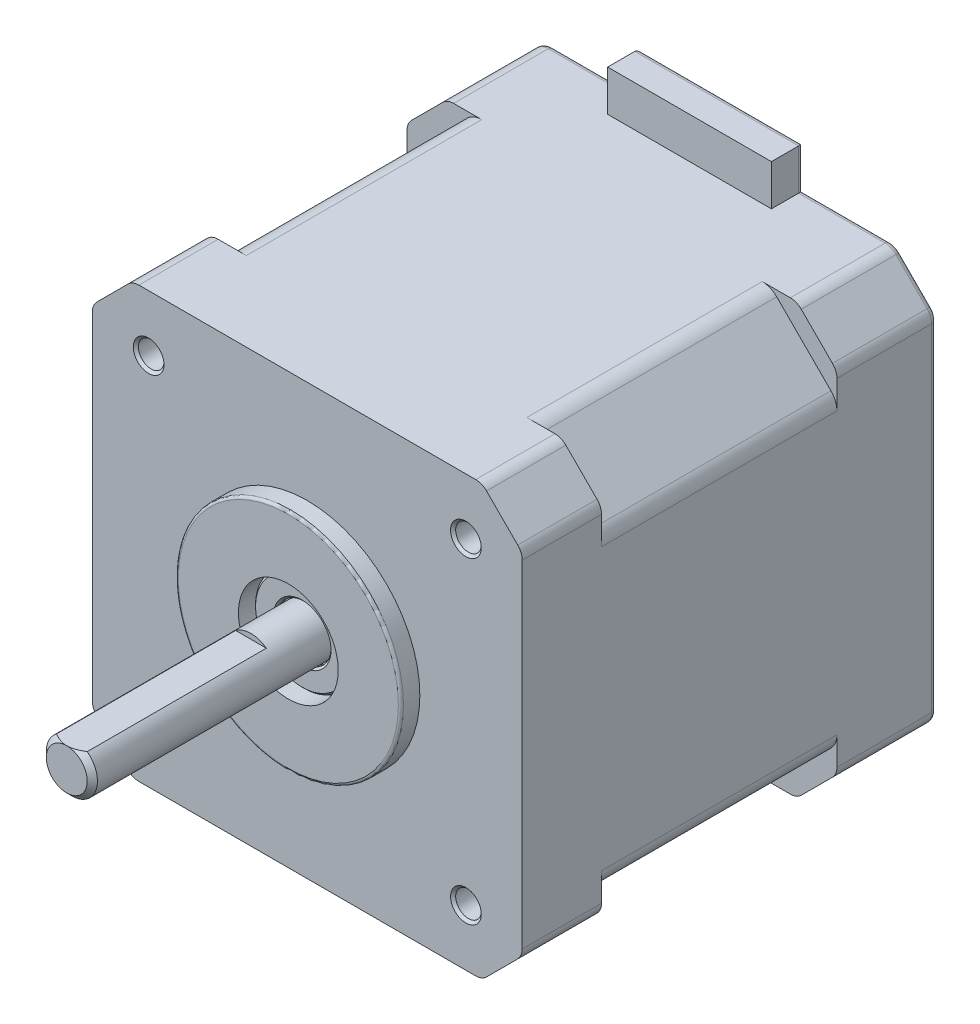
SolidWorks part; units mm, degrees
ref_plane "前视基准面" through (0, 0, 0) normal (0, 0, 1) x (1, 0, 0)
ref_plane "上视基准面" through (0, 0, 0) normal (0, 1, 0) x (1, 0, 0)
ref_plane "右视基准面" through (0, 0, 0) normal (1, 0, 0) x (0, 0, -1)
other "Configuration Table"
sketch "草图1" plane through (0, 0, 0) normal (0, 0, 1) x (1, 0, 0)
  line L1 (-21, 21) -> (21, 21)
  line L2 (-21, 21) -> (-21, -21)
  line L3 (-21, -21) -> (21, -21)
  line L4 (21, 21) -> (21, -21)
  line L5 (-21, 21) -> (21, -21) construction
  line L6 (-21, -21) -> (21, 21) construction
  point P0 (0, 0)
  dimension "D1" = 42
extrude "凸台-拉伸1" add sketch "草图1" along normal blind 40.5
sketch "草图2" plane through (0, 0, 0) normal (0, 0, -1) x (-1, 0, 0)
  line L0 (-21, 21) -> (21, 21) construction
  line L1 (8, 21) -> (-8, 21)
  line L2 (8, 21) -> (8, 25)
  line L3 (8, 25) -> (-8, 25)
  line L4 (-8, 21) -> (-8, 25)
  line L5 (0, 0) -> (0, 31.1942) construction
  dimension "D1" = 16
  dimension "D2" = 4
extrude "凸台-拉伸2" add sketch "草图2" against normal blind 3.15
sketch "草图3" plane through (0, 0, 0) normal (0, 0, -1) x (-1, 0, 0)
  line L0 (-17.075, 21) -> (-21, 17.075)
  line L1 (-21, 21) -> (-8, 21) construction
  line L2 (-21, -21) -> (-21, 21) construction
  line L3 (17.075, 21) -> (21, 17.075)
  line L4 (8, 21) -> (21, 21) construction
  line L5 (21, 21) -> (21, -21) construction
  line L6 (21, -17.075) -> (17.075, -21)
  line L7 (21, -21) -> (-21, -21) construction
  line L8 (-21, -17.075) -> (-17.075, -21)
  line L9 (-17.075, 21) -> (-21, 21)
  line L10 (-21, 21) -> (-21, 17.075)
  line L11 (17.075, 21) -> (21, 21)
  line L12 (21, 21) -> (21, 17.075)
  line L13 (21, -17.075) -> (21, -21)
  line L14 (21, -21) -> (17.075, -21)
  line L15 (-21, -17.075) -> (-21, -21)
  line L16 (-21, -21) -> (-17.075, -21)
  dimension "D1" = 3.925
extrude "切除-拉伸1" cut sketch "草图3" against normal up to next
sketch "草图4" plane through (0, 0, 0) normal (0, 0, -1) x (-1, 0, 0)
  line L0 (-21, 14.532) -> (-14.532, 21)
  line L1 (-21, -17.075) -> (-21, 17.075) construction
  line L2 (-17.075, 21) -> (-8, 21) construction
  line L3 (-14.532, 21) -> (-21, 21)
  line L4 (-21, 21) -> (-21, 14.532)
  line L5 (14.532, 21) -> (21, 14.532)
  line L6 (8, 21) -> (17.075, 21) construction
  line L7 (21, 17.075) -> (21, -17.075) construction
  line L8 (21, 14.532) -> (21, 21)
  line L9 (21, 21) -> (14.532, 21)
  line L10 (21, -14.532) -> (14.532, -21)
  line L11 (17.075, -21) -> (-17.075, -21) construction
  line L12 (14.532, -21) -> (21, -21)
  line L13 (21, -21) -> (21, -14.532)
  line L14 (-14.532, -21) -> (-21, -14.532)
  line L15 (-21, -14.532) -> (-21, -21)
  line L16 (-21, -21) -> (-14.532, -21)
  dimension "D1" = 6.468
extrude "切除-拉伸2" cut sketch "草图4" against normal blind 23 from offset 9.75 offset against normal yes
sketch "草图5" plane through (0, 0, 40.5) normal (0, 0, 1) x (1, 0, 0)
  circle A0 centre (0, 0) radius 11
  circle A1 centre (0, 0) radius 4.875
  dimension "D1" = 22
  dimension "D2" = 9.75
extrude "凸台-拉伸4" add sketch "草图5" along normal blind 1.85
sketch "草图6" plane through (0, 0, 40.5) normal (0, 0, 1) x (1, 0, 0)
  circle A0 centre (0, 0) radius 4.75
  circle A1 centre (0, 0) radius 2.625
  dimension "D1" = 9.5
  dimension "D2" = 5.25
extrude "凸台-拉伸5" add sketch "草图6" along normal blind 0.5
chamfer "倒角1" distance 0.2 angle 45 2 edges at (4.75, 0, 41) (2.625, 0, 41)
sketch "草图7" plane through (0, 0, 40.5) normal (0, 0, 1) x (1, 0, 0)
  circle A0 centre (0, 0) radius 2.5
  dimension "D1" = 5
extrude "凸台-拉伸6" add sketch "草图7" along normal blind 23.5
sketch "草图8" plane through (0, 0, 40.5) normal (0, 0, 1) x (1, 0, 0)
  line L1 (15.5, -15.5) -> (-15.5, -15.5) construction
  line L2 (15.5, -15.5) -> (15.5, 15.5) construction
  line L3 (15.5, 15.5) -> (-15.5, 15.5) construction
  line L4 (-15.5, -15.5) -> (-15.5, 15.5) construction
  line L5 (15.5, -15.5) -> (-15.5, 15.5) construction
  line L6 (15.5, 15.5) -> (-15.5, -15.5) construction
  circle A0 centre (-15.5, 15.5) radius 1.25
  circle A1 centre (15.5, 15.5) radius 1.25
  circle A2 centre (15.5, -15.5) radius 1.25
  circle A3 centre (-15.5, -15.5) radius 1.25
  point P0 (0, 0)
  dimension "D2" = 2.5
  dimension "D1" = 31
extrude "切除-拉伸3" cut sketch "草图8" against normal blind 4
chamfer "倒角2" distance 0.25 angle 45 4 edges at (-14.25, -15.5, 40.5) (16.75, -15.5, 40.5) (16.75, 15.5, 40.5) (-14.25, 15.5, 40.5)
sketch "草图9" plane through (0, 0, 64) normal (0, 0, 1) x (1, 0, 0)
  line L0 (-1.5, 2) -> (1.5, 2)
  circle A0 centre (0, 0) radius 2.5 construction
  circle A1 centre (0, 0) radius 2.5 construction
  arc A2 (1.5, 2) -> (-1.5, 2) centre (0, 0) ccw
  dimension "D1" = 3
extrude "切除-拉伸4" cut sketch "草图9" against normal blind 18
chamfer "倒角3" distance 0.5 angle 45 1 edges at (0, -2.5, 64)
fillet "圆角1" radius 0.25 1 edges at (11, 0, 42.35)
fillet "圆角2" radius 1.5 16 edges at (-21, -17.075, 36.625) (-17.075, -21, 36.625) (-17.075, -21, 4.875) (-21, -17.075, 4.875) (-21, 17.075, 36.625) (-17.075, 21, 36.625) (-17.075, 21, 4.875) (-21, 17.075, 4.875) (17.075, -21, 4.875) (21, -17.075, 4.875) (17.075, -21, 36.625) (21, -17.075, 36.625) (21, 17.075, 4.875) (17.075, 21, 4.875) (21, 17.075, 36.625) (17.075, 21, 36.625)
fillet "圆角3" radius 2 8 edges at (21, -14.532, 21.25) (14.532, -21, 21.25) (-14.532, -21, 21.25) (-21, -14.532, 21.25) (14.532, 21, 21.25) (21, 14.532, 21.25) (-21, 14.532, 21.25) (-14.532, 21, 21.25)
fillet "圆角4" radius 0.5 20 edges at (-12.2268, 21, 0) (-17.0277, 20.8858, 0) (-19.0375, 19.0375, 0) (-20.8858, 17.0277, 0) (-21, 0, 0) (-20.8858, -17.0277, 0) (-19.0375, -19.0375, 0) (-17.0277, -20.8858, 0) (0, -21, 0) (17.0277, -20.8858, 0) (19.0375, -19.0375, 0) (20.8858, -17.0277, 0) (12.2268, 21, 0) (17.0277, 20.8858, 0) (19.0375, 19.0375, 0) (20.8858, 17.0277, 0) (-8, 23, 0) (0, 25, 0) (8, 23, 0) (21, 0, 0)
